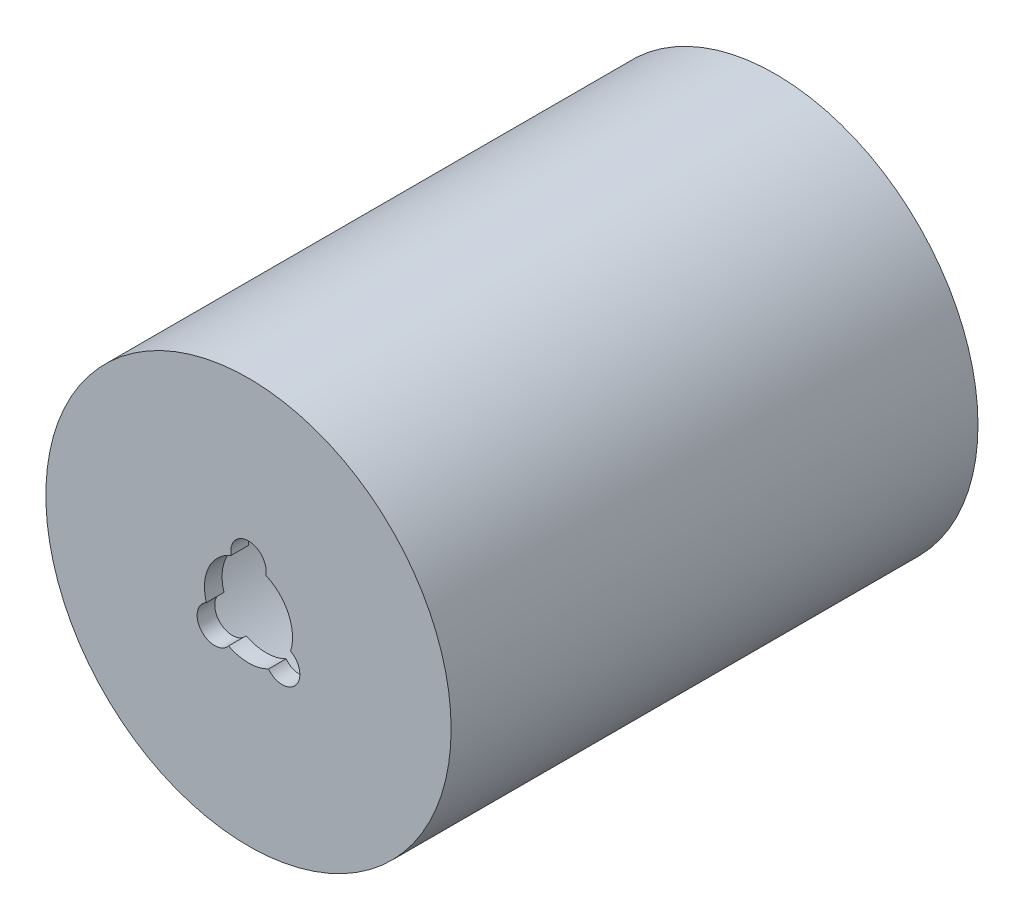
SolidWorks part; units mm, degrees
ref_plane "Front Plane" through (0, 0, 0) normal (0, 0, 1) x (1, 0, 0)
ref_plane "Top Plane" through (0, 0, 0) normal (0, 1, 0) x (1, 0, 0)
ref_plane "Right Plane" through (0, 0, 0) normal (1, 0, 0) x (0, 0, -1)
sketch "Sketch1" plane through (0, 0, 0) normal (1, 0, 0) x (0, 0, -1)
  line L0 (-59.8, 5) -> (-57.8, 5)
  line L1 (-59.8, 0) -> (0, 0)
  line L2 (-59.8, 0) -> (-59.8, 23)
  line L3 (-59.8, 23) -> (0, 23)
  line L4 (0, 0) -> (0, 23)
  line L5 (-1072.3815, 0) -> (1072.3815, 0) construction
  line L6 (-30.8, -974.342) -> (-30.8, 49025.6579)
  line L10 (-57.8, 0) -> (-1.8, 0)
  line L11 (-57.8, 0) -> (-57.8, 17)
  line L12 (-57.8, 17) -> (-1.8, 17)
  line L13 (-1.8, 0) -> (-1.8, 17)
  line L15 (-59.8, 18) -> (0, 18)
  line L16 (-27.3, 23) -> (-27.3, 18)
  line L17 (-1.8, 13) -> (0, 13)
  line L18 (-34.3, 23) -> (-34.3, 18)
  point P14 (-30.8, 17)
  dimension "D3" = 56
  dimension "D1" = 2
  dimension "D2" = 17
  dimension "D6" = 27
  dimension "D5" = 5
  dimension "D9" = 4
  dimension "D4" = 6
  dimension "D7" = 1.8
  dimension "D8" = 1
  dimension "D10" = 7
revolve "Revolve1" add sketch "Sketch1" angle 360 about L5 region at (0, 11.5, 59.4822) region at (0, 20.5, 47.05) region at (0, 20.5, 32.55) region at (0, 17.0263, 12.6526) region at (0, 20.5, 29.05) region at (0, 20.5, 13.65)
ref_axis "Axis1" through (0, 0, -68.4732) along (0, 0, 1)
ref_axis "Axis2" through (0, -974.342, 30.8) along (0, 1, 0)
ref_plane "Plane1" through (0, 0, 30.8) normal (0, 0, 1) x (1, 0, 0)
sketch "Sketch3" plane through (0, 0, 30.8) normal (0, 0, 1) x (1, 0, 0)
  line L0 (0, -999.5695) -> (0, 49000.4305) construction
  line L1 (-340.1578, -934.5758) -> (16760.8494, 46050.0552) construction
  line L2 (-1, 19.9722) -> (1, 19.9722)
  line L3 (338.8634, -931.0195) -> (-16762.1438, 46053.6116) construction
  line L4 (1, 19.9722) -> (4.5053, 16.5181) construction
  line L5 (0, 19.9722) -> (0, 23.1004) construction
  line L6 (2.0302, 19.9722) -> (-0.0328, 19.9722) construction
  line L7 (3.5103, 17.4986) -> (0.2863, 20.6756) construction
  line L8 (1, 19.9722) -> (1.1102, 22.1722) construction
  line L9 (4.5053, 16.5181) -> (4.684, 16.342)
  line L10 (6.5668, 18.0421) -> (7.5928, 20.8612)
  line L11 (-6.5668, 18.0421) -> (-7.5928, 20.8612)
  line L12 (-4.5053, 16.5181) -> (-4.684, 16.342)
  circle A4 centre (0, 0) radius 17 construction
  circle A6 centre (0, 0) radius 17
  circle A8 centre (5.2072, 17.2304) radius 1 construction
  arc A10 (6.5668, 18.0421) -> (-6.5668, 18.0421) centre (0, 0) cw
  circle A13 centre (0, 0) radius 22.2
  spline S0 degree 3 poles (1, 19.9722) (1.8375, 19.9722) (3.4007, 17.6066) (4.5053, 16.5181) knots 0 0 0 0 1 1 1 1
  spline S1 degree 3 poles (-1, 19.9722) (-1.8375, 19.9722) (-3.4007, 17.6066) (-4.5053, 16.5181) knots 0 0 0 0 1 1 1 1
  point P11 (0, 19.9722)
  point P13 (5.8143, 15.9748)
  point P16 (0, 22.2)
  point P20 (0, 19.9722)
  dimension "D2" = 2
  dimension "D4" = 20
  dimension "D1" = 5.2
  dimension "D3" = 1
  dimension "D5" = 2.2
  dimension "D6" = 2.2
extrude "Cut-Extrude1" cut sketch "Sketch3" against normal mid plane 4 contours L10 A13 L11 A10 S1 L2 S0 L9 A6 L12 region at (0, -18.6353, 30.8)
extrude "Cut-Extrude2" cut sketch "Sketch3<5>" against normal mid plane 2 contours A6 | L2 S1 L12 A6 L9 S0 | L11 A13 L10 A10 region at (0, 18.1134, 30.8) region at (0, 0, 30.8) region at (7.661, 19.2401, 30.8)
sketch "Sketch3<5>" plane through (0, 0, 30.8) normal (0, 0, 1) x (1, 0, 0) same geometry as "Sketch3"
ref_plane "Plane2" through (-7.5928, 20.8612, 31.8) normal (-0.9397, -0.342, 0) x (0, 0, 1)
sketch "Sketch5" plane through (0, 0, 59.8) normal (0, 0, 1) x (1, 0, 0)
  line L0 (3.8302, -3.2139) -> (-3.8302, -3.2139) construction
  circle A3 centre (0, 5) radius 2
  circle A4 centre (-3.8302, -3.2139) radius 2
  circle A5 centre (3.8302, -3.2139) radius 2
  circle A6 centre (0, 0) radius 5
  circle A7 centre (0, 0) radius 5 construction
  point P7 (0, -3.2139)
  circle M6 centre (0, 0) radius 5
extrude "Cut-Extrude3" cut sketch "Sketch5" against normal up to next contours A6 A4 M6 | A3 M6 | A6 A5 M6 region at (0, 5.7727, 59.8) region at (-4.4222, -3.7106, 59.8) region at (4.4222, -3.7106, 59.8)
equation "\"key_pin_length\"= 25.00mm"
equation "\"key_pin_dia\"= 20.00mm"
equation "\"driver_pin_travel\"= 3.00mm"
equation "\"driver_pin_dia\"= 3mm"
equation "\"plug_wall_thickness\" = 2mm"
equation "\"plug_spring_solid_length\"= 2mm"
equation "\"plug_length\"= 2 * \"key_pin_length\" + 2 * \"plug_wall_thickness\" + \"plug_spring_solid_length\""
equation "\"D3@Sketch1\"= \"plug_length\""
equation "\"D6@Sketch1\"= \"plug_wall_thickness\" + \"key_pin_length\""
equation "\"D7@Sketch1\"=\"D1@Sketch1\"-\"allowance\""
equation "\"driver_pin_head_dia\" = 2mm"
equation "\"D1@Sketch3\"=\"driver_pin_head_dia\"+\"driver_pin_travel\"+\"allowance\""
equation "\"true_gate_depth\" = 1.25mm"
equation "\"D4@Sketch1\"= \"driver_pin_head_dia\" + \"driver_pin_travel\" + 1mm"
equation "\"driver_pin_neck_dia\"= 2.00mm"
equation "\"driver_pin_head_length\" = 2mm"
equation "\"D1@Cut-Extrude1\"= \"driver_pin_neck_dia\" + \"driver_pin_head_length\""
equation "\"D1@Cut-Extrude2\"=\"driver_pin_neck_dia\""
equation "\"plug_dia\"= \"key_pin_dia\" + 2*(\"driver_pin_travel\" + 1mm + \"plug_spring_solid_length\" + 1mm)"
equation "\"D2@Sketch1\"=\"plug_dia\"/2"
equation "\"D2@Sketch3\"=\"driver_pin_head_dia\""
equation "\"D5@Sketch3\"=\"driver_pin_head_dia\"+\"allowance\""
equation "\"D6@Sketch3\"=\"driver_pin_head_dia\"+\"allowance\""
equation "\"key_notches_dia\" = 4mm"
equation "\"key_notches_offset_angle\" = 25deg"
equation "\"key_offset_angle\" = 60deg"
equation "\"key_offset_len\" = 6mm"
equation "\"allowance\" = 0.2mm"
